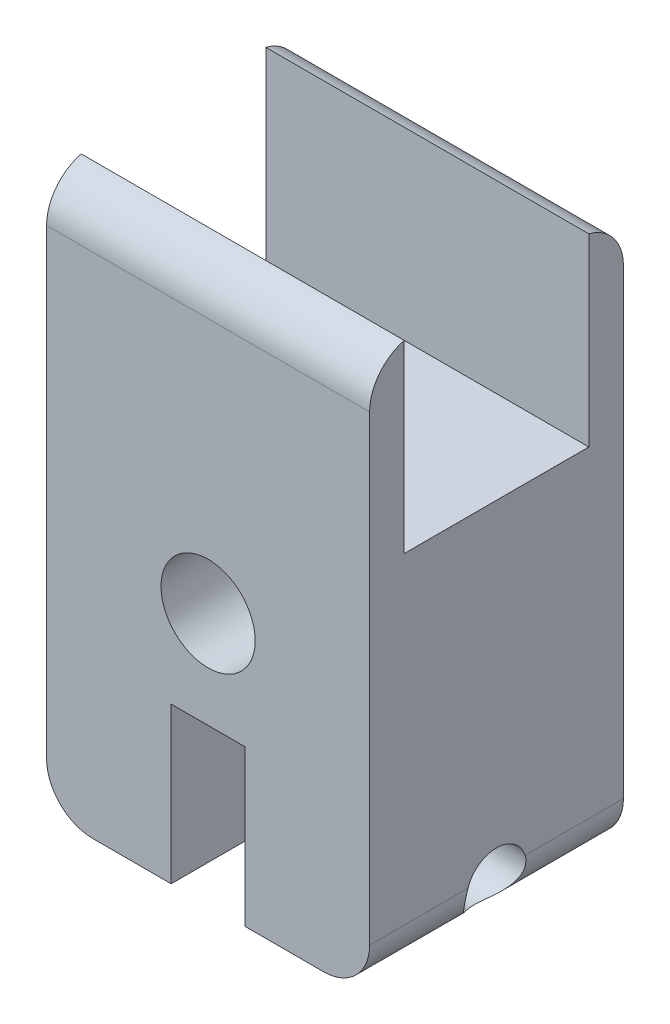
SolidWorks part; units mm, degrees
ref_plane "Alzado" through (0, 0, 0) normal (0, 0, 1) x (1, 0, 0)
ref_plane "Planta" through (0, 0, 0) normal (0, 1, 0) x (1, 0, 0)
ref_plane "Vista lateral" through (0, 0, 0) normal (1, 0, 0) x (0, 0, -1)
sketch "Croquis1" plane through (0, 0, 0) normal (0, 0, 1) x (1, 0, 0)
  line L0 (0, 0) -> (35, -35) construction
  line L2 (0, 0) -> (35, 0)
  line L3 (0, 0) -> (0, -35)
  line L4 (0, -35) -> (35, -35)
  line L5 (35, 0) -> (35, -35)
  circle A0 centre (17.5, -17.5) radius 11
  dimension "D2" = 22
  dimension "D1" = 35
extrude "EntradaBase" add sketch "Croquis1" along normal blind 3.5
sketch "Croquis2" plane through (0, 0, 3.5) normal (0, 0, 1) x (1, 0, 0)
  line L0 (35, 0) -> (0, -35) construction
  line L1 (0, 0) -> (35, 0)
  line L2 (0, 0) -> (0, -35)
  line L3 (0, -35) -> (35, -35)
  line L4 (35, 0) -> (35, -35)
  circle A0 centre (17.5, -17.5) radius 5.1
  dimension "D1" = 10.2
extrude "EntradaCavidad" add sketch "Croquis2" along normal blind 24
fillet "Redondeo1" radius 5 2 edges at (35, -35, 13.75) (0, -35, 13.75)
sketch "Croquis4" plane through (0, 0, 0) normal (-1, 0, 0) x (0, 0, 1)
  line L0 (27.5, -35) -> (27.5, -30) construction
  line L1 (0, -30) -> (27.5, -30)
  line L2 (0, -30) -> (0, -40.86)
  line L3 (0, -40.86) -> (27.5, -40.86)
  line L4 (27.5, -30) -> (27.5, -40.86)
  line L6 (0, -40.86) -> (27.5, -40.86)
  line L7 (0, -40.86) -> (0, -44.86)
  line L8 (0, -44.86) -> (27.5, -44.86)
  line L9 (27.5, -40.86) -> (27.5, -44.86)
  circle A0 centre (13.75, -40.86) radius 3.25
  line M8 (0, -30) -> (27.5, -30)
  dimension "D2" = 6.5
  dimension "D1" = 10.86
  dimension "D3" = 4
extrude "BarrenoRodamiento" add sketch "Croquis4" against normal through all contours A0 L3 L4 L2 M8 | A0 L3 L7 L8 L9 region at (0, -35.1917, 13.75) region at (0, -41.1379, 5.25)
sketch "Croquis5" plane through (0, 0, 0) normal (0, 0, -1) x (-1, 0, 0)
  line L0 (-17.5, -17.5) -> (-17.5, -49.2096) construction
  line L1 (-35, -44.86) -> (0, -44.86) construction
  line L2 (-13.5, -28) -> (-21.5, -28)
  line L3 (-17.5, -28) -> (-17.5, -44.86)
  line L4 (-13.5, -44.86) -> (-21.5, -44.86)
  line L5 (-21.5, -28) -> (-21.5, -44.86)
  line L6 (-13.5, -28) -> (-13.5, -44.86)
  dimension "D1" = 10.5
  dimension "D2" = 4
extrude "EntradaRodamiento" cut sketch "Croquis5" against normal through all contours L2 L5 L4 L6
fillet "Detalle2" radius 5 2 edges at (35, -44.86, 13.75) (0, -44.86, 13.75)
sketch "Croquis10" plane through (0, 0, 0) normal (-1, 0, 0) x (0, 0, 1)
  line L0 (13.75, 0) -> (13.75, 15) construction
  line L1 (27.5, 0) -> (0, 0) construction
  line L2 (3.75, 15) -> (3.75, 0)
  line L3 (0, 0) -> (13.75, 0)
  line L4 (0, 0) -> (0, 15)
  line L5 (0, 15) -> (13.75, 15)
  line L6 (13.75, 0) -> (13.75, 15)
  line L8 (3.75, 15) -> (23.75, 15)
  line L9 (3.75, 15) -> (3.75, -5)
  line L10 (3.75, -5) -> (23.75, -5)
  line L11 (23.75, 15) -> (23.75, -5)
  line L12 (27.5, 0) -> (23.75, 0)
  line L13 (27.5, 0) -> (27.5, 15)
  line L14 (27.5, 15) -> (23.75, 15)
  line L15 (23.75, 0) -> (23.75, 15)
  dimension "D1" = 15
  dimension "D2" = 20
  dimension "D3" = 20
  dimension "D4" = 10
extrude "Saliente-Extruir4" add sketch "Croquis10" against normal through all contours L5 L4 L14 L2 | L13 L14 L11 region at (0, 7.5, 1.875) region at (0, 7.5, 25.625)
fillet "Redondeo5" radius 5 2 edges at (17.5, 15, 0) (17.5, 15, 27.5)
sketch "Croquis11" plane through (0, 0, 0) normal (-1, 0, 0) x (0, 0, 1)
  line L1 (3.75, 15) -> (23.75, 15)
  line L2 (3.75, 15) -> (3.75, -5)
  line L3 (3.75, -5) -> (23.75, -5)
  line L4 (23.75, 15) -> (23.75, -5)
  dimension "D1" = 20
  dimension "D2" = 20
extrude "Cortar-Extruir5" cut sketch "Croquis11" against normal through all
